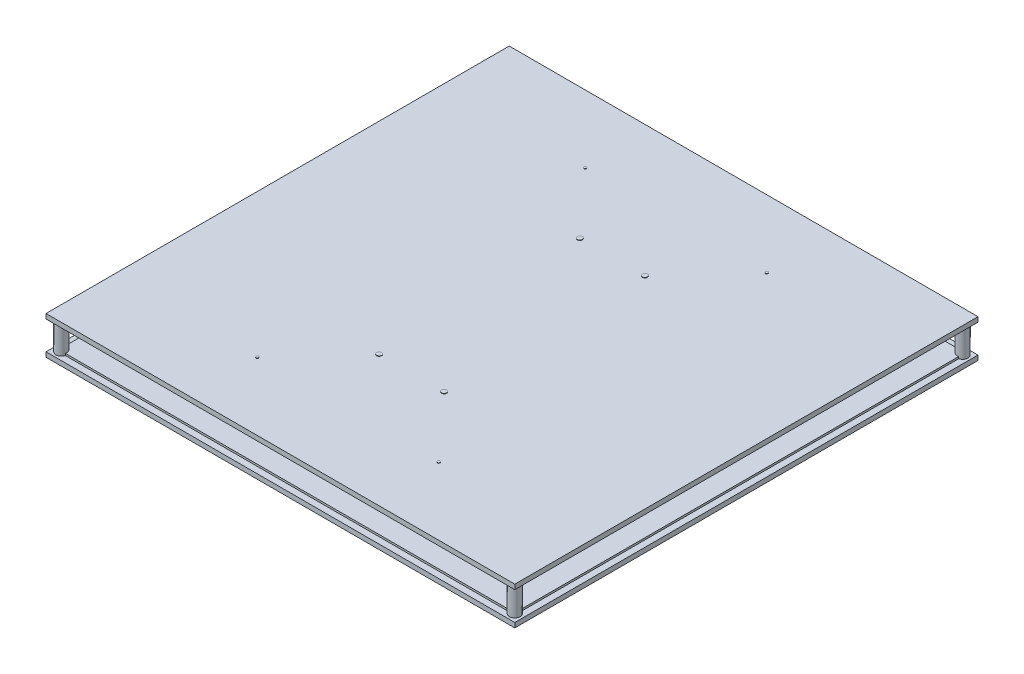
SolidWorks part; units mm, degrees
ref_plane "Front Plane" through (0, 0, 0) normal (0, 0, 1) x (1, 0, 0)
ref_plane "Top Plane" through (0, 0, 0) normal (0, 1, 0) x (1, 0, 0)
ref_plane "Right Plane" through (0, 0, 0) normal (1, 0, 0) x (0, 0, -1)
sketch "Sketch1" plane through (0, 0, 0) normal (0, 1, 0) x (1, 0, 0)
  line L1 (-155.3961, -153.5521) -> (155.3961, -153.5521)
  line L2 (-155.3961, -153.5521) -> (-155.3961, 153.5521)
  line L3 (-155.3961, 153.5521) -> (155.3961, 153.5521)
  line L4 (155.3961, -153.5521) -> (155.3961, 153.5521)
  line L5 (-155.3961, -153.5521) -> (155.3961, 153.5521) construction
  line L6 (-155.3961, 153.5521) -> (155.3961, -153.5521) construction
  point P0 (0, 0)
extrude "Boss-Extrude1" add sketch "Sketch1" along normal blind 3.175 contours L2 L1 L4 L3
sketch "Sketch2" plane through (0, 3.175, 0) normal (0, 1, 0) x (1, 0, 0)
  line L13 (151.1543, 149.3103) -> (-151.1543, 149.3103)
  line L14 (151.1543, 149.3103) -> (151.1543, -149.3103)
  line L15 (151.1543, -149.3103) -> (-151.1543, -149.3103)
  line L16 (-151.1543, 149.3103) -> (-151.1543, -149.3103)
extrude "Boss-Extrude2" add sketch "Sketch2" along normal blind 1.27 contours L14 L13 L16 L15
sketch "Sketch4" plane through (0, 0, -153.5521) normal (0, 0, -1) x (-1, 0, 0)
  line L0 (155.3961, 3.175) -> (155.3961, 25.1714)
  line L1 (-155.3961, 3.175) -> (-155.3961, 25.1714)
sketch "Sketch5" plane through (0, 0, 153.5521) normal (0, 0, 1) x (1, 0, 0)
  line L0 (155.3961, 3.175) -> (155.3961, 25.1714)
  line L1 (-155.3961, 3.175) -> (-155.3961, 25.1714)
sketch3d "3DSketch1"
  line L0 (-155.3961, 25.1714, -153.5521) -> (-155.3961, 25.1714, 153.5521)
  line L1 (-155.3961, 25.1714, 153.5521) -> (155.3961, 25.1714, 153.5521)
  line L2 (155.3961, 25.1714, 153.5521) -> (155.3961, 25.1714, -153.5521)
  line L3 (155.3961, 25.1714, -153.5521) -> (-155.3961, 25.1714, -153.5521)
extrude "Boss-Extrude4" add sketch "3DSketch1" along direction (0, -1, 0) on the side of the normal blind 3.175 separate body contours L0 L1 L2 L3
sketch "Sketch6" plane through (0, 25.1714, 0) normal (0, 1, 0) x (1, 0, 0)
  line L1 (155.3961, 153.5521) -> (-155.3961, 153.5521) construction
  line L5 (0, -153.5521) -> (0, 153.5521)
  line L6 (-155.3961, -153.5521) -> (155.3961, -153.5521) construction
  line L7 (-155.3961, 0) -> (155.3961, 0)
  line L8 (-155.3961, 153.5521) -> (-155.3961, -153.5521) construction
  line L9 (155.3961, -153.5521) -> (155.3961, 153.5521) construction
  circle A0 centre (60.1461, 108.7163) radius 0.911
  circle A1 centre (21.5381, 66.5523) radius 1.6837
  circle A2 centre (-21.5381, 66.5523) radius 1.6837
  circle A3 centre (-60.1461, 108.7163) radius 0.911
  circle A4 centre (21.5381, -66.5523) radius 1.6837
  circle A5 centre (60.1461, -108.7163) radius 0.911
  circle A6 centre (-21.5381, -66.5523) radius 1.6837
  circle A7 centre (-60.1461, -108.7163) radius 0.911
  dimension "D1" = 44.8358
  dimension "D2" = 44.8358
  dimension "D3" = 44.8358
  dimension "D4" = 44.8358
  dimension "D5" = 86.9998
  dimension "D6" = 3.3675
extrude "Boss-Extrude7" add sketch "Sketch6" along normal blind 0.254 contours A7 | A6 | A3 | A2 | A1 | A0 | A6 | A4 | A5 region at (-21.5381, 25.1714, 66.5523) region at (-60.1461, 25.1714, 108.7163)
sketch "Sketch7" plane through (0, 0, 0) normal (0, -1, 0) x (1, 0, 0)
  line L0 (-155.3961, 153.5521) -> (-150.3161, 153.5521)
  line L1 (-155.3961, 153.5521) -> (155.3961, 153.5521) construction
  circle A0 centre (-150.3161, 148.4721) radius 3.556
  circle A1 centre (150.3161, 148.4721) radius 3.556
  circle A2 centre (150.3161, -148.4721) radius 3.556
  circle A3 centre (-150.3161, -148.4721) radius 3.556
extrude "Boss-Extrude8" add sketch "Sketch7" against normal blind 23.876 contours A3 | A2 | A1 | A0
